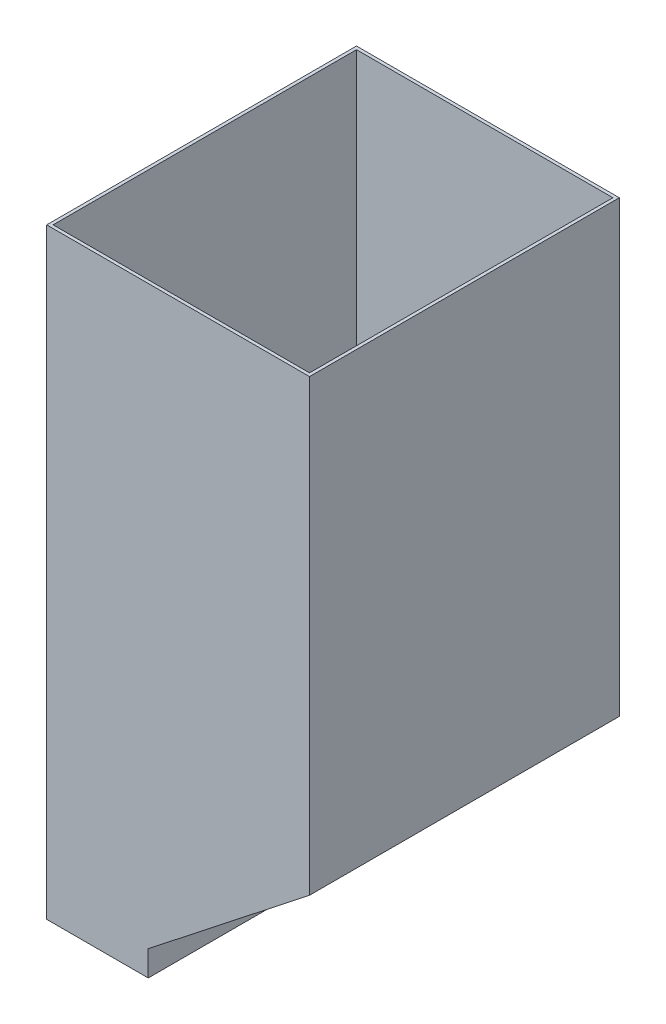
SolidWorks part; units mm, degrees
other "Marquage1"
sketch "Esquisse3" plane through (127, 224.79, 233.68) normal (0.5774, 0.5773, 0.5774) x (0.7071, 0, -0.7071)
material "Oak"
ref_plane "Plan de face" through (0, 0, 0) normal (0, 0, 1) x (1, 0, 0)
ref_plane "Plan de dessus" through (0, 0, 0) normal (0, 1, 0) x (1, 0, 0)
ref_plane "Plan de droite" through (0, 0, 0) normal (1, 0, 0) x (0, 0, -1)
sketch "Esquisse1" plane through (0, 0, 0) normal (0, 0, 1) x (1, 0, 0)
  line L0 (-29.9, -288.29) -> (131.5, -161.29)
  line L5 (-131.5, 288.29) -> (131.5, 288.29)
  line L6 (-131.5, 288.29) -> (-131.5, -288.29)
  line L8 (131.5, 288.29) -> (131.5, -161.29)
  line L9 (-131.5, -288.29) -> (-36.25, -288.29)
  line L10 (-36.25, -288.29) -> (-36.25, -313.69)
  line L11 (-36.25, -313.69) -> (-29.9, -313.69)
  line L12 (-29.9, -288.29) -> (-29.9, -313.69)
  point P0 (-131.5, 0)
  point P5 (0, 288.29)
  dimension "D1" = 6.35
  dimension "D2" = 101.6
  dimension "D3" = 449.58
  dimension "D4" = 25.4
  dimension "D5" = 576.58
  dimension "D6" = 263
extrude "Boss.-Extru.1" add sketch "Esquisse1" along normal mid plane 310
ref_plane "Plan1" through (0, 0, 151.825) normal (0, 0, 1) x (1, 0, 0)
sketch "Esquisse2" plane through (0, 0, 151.825) normal (0, 0, 1) x (1, 0, 0)
  line L0 (-128.325, 288.29) -> (-128.325, -288.29)
  line L1 (-128.325, -288.29) -> (-35.0344, -288.29)
  line L2 (-35.0344, -288.29) -> (128.325, -159.7482)
  line L3 (128.325, -159.7482) -> (128.325, 288.29)
  line L4 (128.325, 288.29) -> (-128.325, 288.29)
  line L5 (-131.5, 288.29) -> (-131.5, -288.29) construction
  line L6 (131.5, -161.29) -> (131.5, 288.29) construction
  line L7 (-29.9, -288.29) -> (131.5, -161.29) construction
  line L8 (-131.5, -288.29) -> (-36.25, -288.29) construction
  line L9 (131.5, 288.29) -> (-131.5, 288.29) construction
  dimension "D1" = 3.175
  dimension "D2" = 3.175
  dimension "D3" = 3.175
extrude "Enlèv. mat.-Extru.1" cut sketch "Esquisse2" against normal blind 303.65
sketch "Esquisse4" plane through (-36.25, 0, 0) normal (-1, 0, 0) x (0, 0, 1)
  line L0 (155, -313.69) -> (-155, -313.69) construction
  line L1 (-155, -288.29) -> (-148.65, -288.29)
  line L2 (-155, -288.29) -> (-155, -313.69)
  line L3 (-155, -313.69) -> (-148.65, -313.69)
  line L5 (-148.65, -313.69) -> (-148.65, -288.29)
  dimension "D1" = 6.35
extrude "Boss.-Extru.2" add sketch "Esquisse4" along normal blind 95.25
mirror "Symétrie1" about plane through (0, 0, 0) normal (0, 0, 1) of "Boss.-Extru.2"
